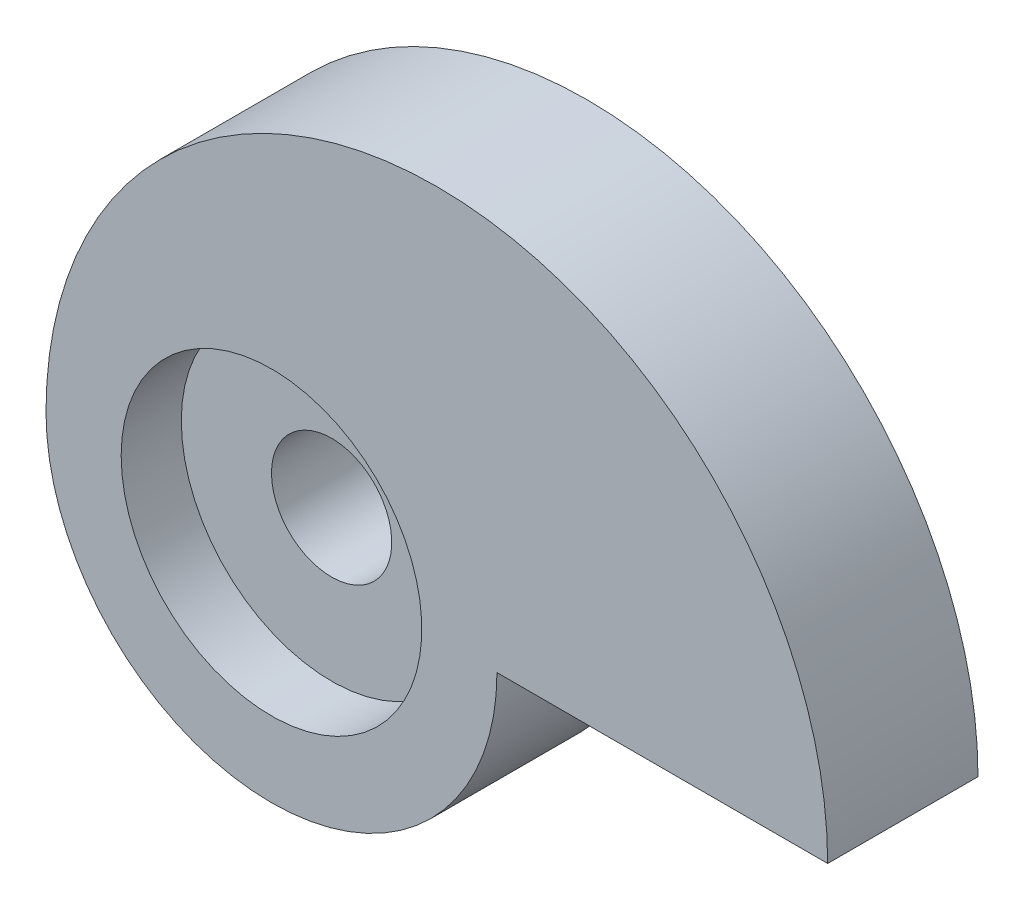
SolidWorks part; units mm, degrees
ref_plane "Front Plane" through (0, 0, 0) normal (0, 0, 1) x (1, 0, 0)
ref_plane "Top Plane" through (0, 0, 0) normal (0, 1, 0) x (1, 0, 0)
ref_plane "Right Plane" through (0, 0, 0) normal (1, 0, 0) x (0, 0, -1)
sketch "Sketch1" plane through (0, 0, 0) normal (0, 0, 1) x (1, 0, 0)
  line L0 (-13, 0) -> (13, 0) construction
  line L2 (2, 0) -> (13, 0)
  arc A0 (13, 0) -> (-13, 0) centre (0, 0) ccw
  circle A3 centre (-5.5, 0) radius 2
  arc A4 (-13, 0) -> (2, 0) centre (-5.5, 0) ccw
  dimension "D1" = 26
  dimension "D2" = 4
  dimension "D3" = 7.5
extrude "Boss-Extrude1" add sketch "Sketch1" along normal blind 5
sketch "Sketch3" plane through (0, 0, 0) normal (0, 0, 1) x (1, 0, 0)
  circle A0 centre (-5.5, 0) radius 5
  circle A1 centre (-5.5, 0) radius 2 construction
  circle A2 centre (-5.5, 0) radius 2
  dimension "D1" = 10
extrude "Boss-Extrude2" add sketch "Sketch3" against normal blind 5
sketch "Sketch4" plane through (0, 0, -5) normal (0, 0, -1) x (-1, 0, 0)
  line L1 (-1.0014, -1) -> (12.0014, -1)
  line L2 (-1.0014, -1) -> (-1.0014, 1)
  line L3 (-1.0014, 1) -> (12.0014, 1)
  line L4 (12.0014, -1) -> (12.0014, 1)
  line L5 (-1.0014, -1) -> (12.0014, 1) construction
  line L6 (-1.0014, 1) -> (12.0014, -1) construction
  point P0 (5.5, 0)
  dimension "D1" = 2
extrude "Cut-Extrude1" cut sketch "Sketch4" against normal blind 3
fillet "Fillet1" radius 1 4 edges at (-8.8155, 1, -2) (-8.8155, -1, -2) (-2.1845, -1, -2) (-2.1845, 1, -2)
sketch "Sketch5" plane through (0, 0, 5) normal (0, 0, -1) x (-1, 0, 0)
  circle A1 centre (5.5, 0) radius 5
  circle A2 centre (5.5, 0) radius 2 construction
  dimension "D1" = 10
extrude "Cut-Extrude2" cut sketch "Sketch5" along normal blind 2
fillet "Fillet2" radius 1.5 1 edges at (-0.5, 0, 0)
